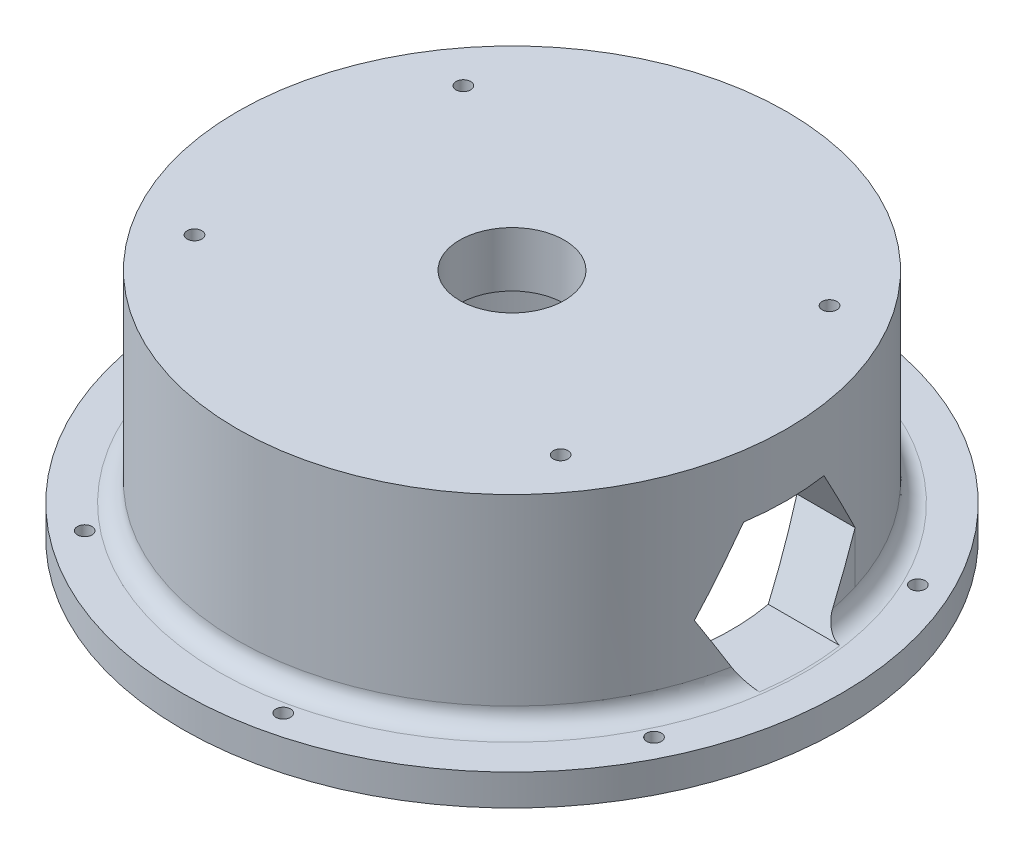
SolidWorks part; units mm, degrees
ref_plane "Alzado" through (0, 0, 0) normal (0, 0, 1) x (1, 0, 0)
ref_plane "Planta" through (0, 0, 0) normal (0, 1, 0) x (1, 0, 0)
ref_plane "Vista lateral" through (0, 0, 0) normal (1, 0, 0) x (0, 0, -1)
sketch "Croquis4" plane through (0, 0, 0) normal (0, 1, 0) x (1, 0, 0)
  circle A0 centre (0, 0) radius 75
  circle A1 centre (0, 0) radius 90
  circle A2 centre (-83, 0) radius 2
  circle A3 centre (-51.7497, 64.892) radius 2
  circle A4 centre (18.4692, 80.919) radius 2
  circle A5 centre (74.7804, 36.0124) radius 2
  circle A6 centre (74.7804, -36.0124) radius 2
  circle A7 centre (18.4692, -80.919) radius 2
  circle A8 centre (-51.7497, -64.892) radius 2
  point P21 (0, 0)
  dimension "D1" = 150
  dimension "D3" = 4
  dimension "D4" = 7
  dimension "D2" = 15
  dimension "D5" = 7
extrude "Saliente-Extruir2" add sketch "Croquis4" along normal blind 60 contours A0
shell "Vaciado1" thickness 15 removed face at (0, 0, 75)
sketch "Croquis5" plane through (0, 0, 0) normal (1, 0, 0) x (0, 0, -1)
  line L0 (-75, 0) -> (75, 0) construction
  line L1 (10.9697, 5.05) -> (21.9393, 24.05)
  line L2 (21.9393, 24.05) -> (10.9697, 43.05)
  line L3 (10.9697, 43.05) -> (-10.9697, 43.05)
  line L4 (-10.9697, 43.05) -> (-21.9393, 24.05)
  line L5 (-21.9393, 24.05) -> (-10.9697, 5.05)
  line L6 (-10.9697, 5.05) -> (10.9697, 5.05)
  circle A0 centre (0, 24.05) radius 19 construction
  dimension "D1" = 38
  dimension "D2" = 5.05
extrude "Cortar-Extruir1" cut sketch "Croquis5" against normal blind 60 from surface starting at face at (0, 60, 75)
sketch "Croquis6" plane through (0, 60, 0) normal (0, 1, 0) x (1, 0, 0)
  circle A0 centre (0, 0) radius 14.285
  dimension "D1" = 28.57
extrude "Cortar-Extruir2" cut sketch "Croquis6" against normal through all
extrude "Saliente-Extruir5" add sketch "Croquis4<3>" along normal blind 8.5 from offset 3.5 offset against normal yes
sketch "Croquis4<3>" plane through (0, 0, 0) normal (0, 1, 0) x (1, 0, 0) same geometry as "Croquis4"
fillet "Redondeo2" radius 5 1 edges at (0, 5, 75)
sketch "Croquis7" plane through (0, 60, 0) normal (0, 1, 0) x (1, 0, 0)
  line L0 (0, 0) -> (0, 45.9649) construction
  line L1 (0, 0) -> (42.7647, 0) construction
  circle A0 centre (-50.2781, 36.992) radius 2
  circle A2 centre (51.7019, 34.9743) radius 2
  circle A3 centre (-51.7019, -34.9743) radius 2
  circle A4 centre (50.2781, -36.992) radius 2
extrude "Cortar-Extruir3" cut sketch "Croquis7" against normal blind 12
